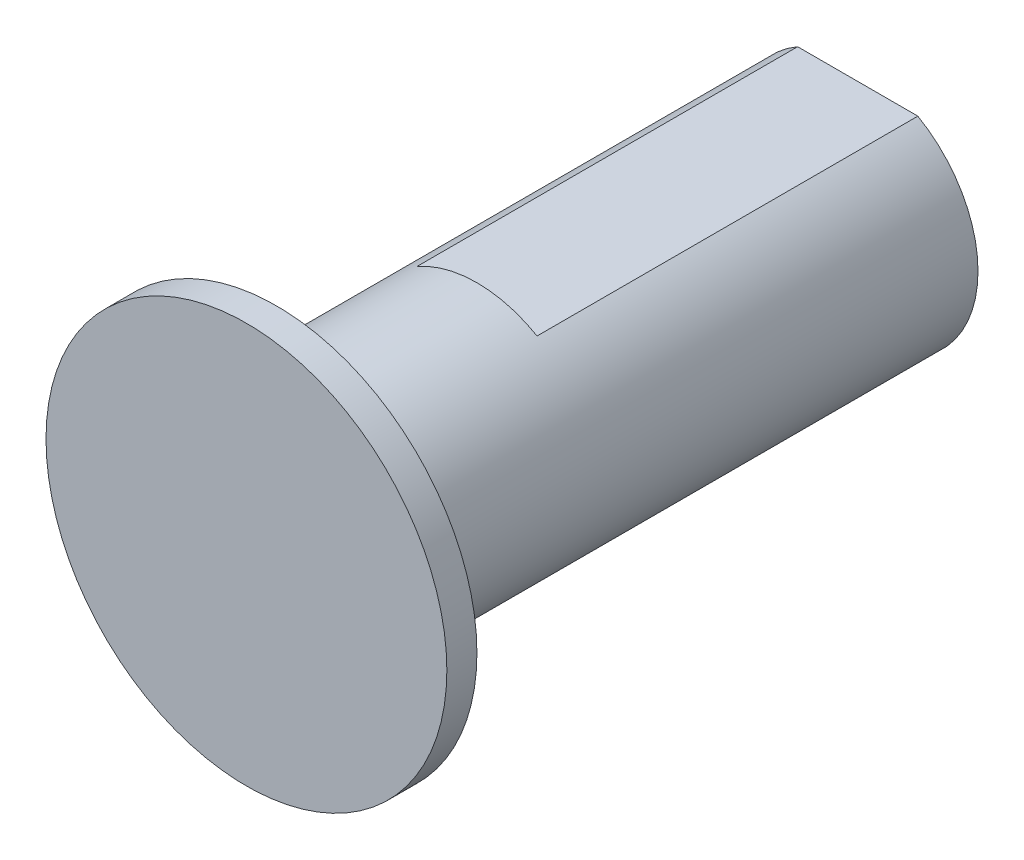
SolidWorks part; units mm, degrees
material "6061 Alloy"
ref_plane "Front Plane" through (0, 0, 0) normal (0, 0, 1) x (1, 0, 0)
ref_plane "Top Plane" through (0, 0, 0) normal (0, 1, 0) x (1, 0, 0)
ref_plane "Right Plane" through (0, 0, 0) normal (1, 0, 0) x (0, 0, -1)
sketch "Sketch1" plane through (0, 0, 0) normal (0, 0, 1) x (1, 0, 0)
  line L0 (-3, 5.1962) -> (3, 5.1962)
  circle A0 centre (0, 0) radius 6
  dimension "D1" = 12
  dimension "D2" = 6
extrude "Boss-Extrude1" add sketch "Sketch1" along normal blind 29 contours A0
sketch "Sketch2" plane through (0, 0, 0) normal (0, 0, -1) x (-1, 0, 0)
  line L0 (-3, 5.1962) -> (3, 5.1962)
  circle A1 centre (0, 0) radius 6 construction
  circle A2 centre (0, 0) radius 6
  circle M3 centre (0, 0) radius 6
  dimension "D1" = 6
extrude "Cut-Extrude1" cut sketch "Sketch2" against normal blind 19 contours L0 M3 region at (0, 5.5196, 0)
sketch "Sketch3" plane through (0, 0, 29) normal (0, 0, 1) x (1, 0, 0)
  circle A0 centre (0, 0) radius 10
  dimension "D1" = 20
extrude "Boss-Extrude2" add sketch "Sketch3" along normal blind 1.5
